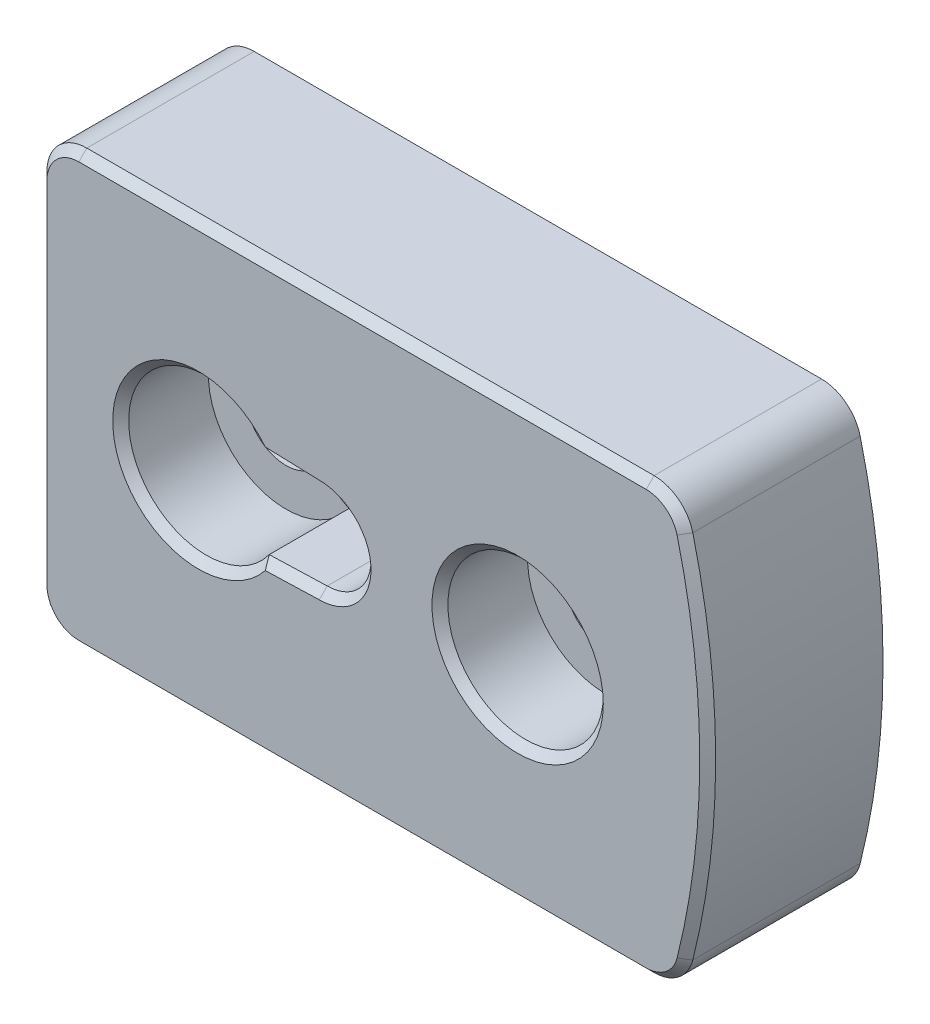
SolidWorks part; units mm, degrees
ref_plane "Front Plane" through (0, 0, 0) normal (0, 0, 1) x (1, 0, 0)
ref_plane "Top Plane" through (0, 0, 0) normal (0, 1, 0) x (1, 0, 0)
ref_plane "Right Plane" through (0, 0, 0) normal (1, 0, 0) x (0, 0, -1)
sketch "Sketch1" plane through (0, 0, 0) normal (0, 0, 1) x (1, 0, 0)
  line L0 (-10, 13.5) -> (-10, -13.5) construction
  line L1 (-20, -13.5) -> (20, -13.5)
  line L2 (-20, -13.5) -> (-20, 13.5)
  line L3 (-20, 13.5) -> (20, 13.5)
  line L5 (-20, -13.5) -> (20, 13.5) construction
  line L6 (-20, 13.5) -> (20, -13.5) construction
  line L7 (10.0266, 13.5) -> (10.0266, -13.5) construction
  line L8 (-8.92, 0) -> (-8.92, -38.6748) construction
  line L13 (-8.92, -38.6748) -> (-10.28, -38.6748) construction
  line L14 (-10.28, -38.6748) -> (-10.28, 0) construction
  line L15 (-2.42, 6.5) -> (43.4398, 6.5) construction
  line L16 (43.4398, 6.5) -> (43.4398, 7.86) construction
  line L17 (43.4398, 7.86) -> (-2.42, 7.86) construction
  line L18 (20, -13.5) -> (19.9199, -28.5934)
  circle A0 centre (-2.42, 0) radius 6.5
  arc A1 (-10.28, 0) -> (-2.42, 7.86) centre (-2.42, 0) cw construction
  arc A2 (20, 13.5) -> (20, -13.5) centre (-25.7558, 0) cw
  point P0 (-2.4466, -2.4466)
  point P7 (21.95, 0)
  dimension "D3" = 13
  dimension "D6" = 1.36
  dimension "D8" = 17.58
  dimension "D9" = 1.95
  dimension "D1" = 5.64
  dimension "D2" = 40
  dimension "D4" = 10
  dimension "D5" = 27
  dimension "D7" = 1.36
extrude "Boss-Extrude1" add sketch "Sketch1" along normal blind 11 contours L1 L3 L2 A0 | A0 region at (-19.5011, 0, 0) region at (-2.42, 0, 0)
sketch "Sketch2" plane through (0, 0, 11) normal (0, 0, 1) x (1, 0, 0)
  line L0 (-10, 13.5) -> (-10, -13.5) construction
  line L1 (10.0266, 13.5) -> (10.0266, -13.5) construction
  circle A0 centre (-10, 0) radius 2.5
  circle A1 centre (10.0266, 0) radius 2.5
  dimension "D1" = 5
extrude "Cut-Extrude1" cut sketch "Sketch2" against normal through all
sketch "Sketch3" plane through (0, 0, 11) normal (0, 0, 1) x (1, 0, 0)
  line L0 (-10, 13.5) -> (-10, -13.5) construction
  line L1 (10.0266, 13.5) -> (10.0266, -13.5) construction
  circle A0 centre (-10, 0) radius 4.875
  circle A1 centre (10.0266, 0) radius 4.875
  dimension "D1" = 9.75
extrude "Cut-Extrude2" cut sketch "Sketch3" against normal offset from surface (5.5 mm away) 5.5 up to face at (-7.5, 0, 0)
sketch "Sketch4" plane through (0, 0, 11) normal (0, 0, 1) x (1, 0, 0)
  circle A0 centre (-2.42, 0) radius 2.75
  dimension "D1" = 5.5
extrude "Cut-Extrude3" cut sketch "Sketch4" against normal through all
sketch "Sketch5" plane through (0, 0, 0) normal (0, 0, -1) x (-1, 0, 0)
  line L1 (6.72, -2.4826) -> (6.72, 2.4826)
  line L2 (6.72, 2.4826) -> (2.42, 4.9652)
  line L3 (2.42, 4.9652) -> (-1.88, 2.4826)
  line L4 (-1.88, 2.4826) -> (-1.88, -2.4826)
  line L5 (-1.88, -2.4826) -> (2.42, -4.9652)
  line L6 (2.42, -4.9652) -> (6.72, -2.4826)
  line L7 (20, -13.5) -> (20, 13.5) construction
  circle A0 centre (2.42, 0) radius 4.3 construction
  dimension "D1" = 8.6
extrude "Cut-Extrude4" cut sketch "Sketch5" against normal up to surface (5.5 mm away) up to face at (-10.0225, 0, 5.5)
fillet "Fillet1" radius 2.5 4 edges at (-20, -13.5, 5.5) (-20, 13.5, 5.5) (20, -13.5, 5.5) (20, 13.5, 5.5)
chamfer "Chamfer1" distance 0.5 angle 45 8 edges at (0.2956, -13.5, 11) (-19.2678, -12.7678, 11) (-20, 0, 11) (-19.2678, 12.7678, 11) (0.2956, 13.5, 11) (19.629, -12.9711, 11) (21.95, 0, 11) (19.629, 12.9711, 11)
sketch "Sketch6" plane through (0, 0, 11) normal (0, 0, 1) x (1, 0, 0)
  line L5 (-6.0563, 2.8658) -> (-2.42, 2.75)
  line L6 (-6.0563, -2.8658) -> (-2.42, -2.75)
  line L7 (-6.0563, 2.8658) -> (-2.42, 4.9652) construction
  line L9 (-6.0563, -2.8658) -> (-6.72, -2.4826)
  line L12 (-6.72, 2.4826) -> (-2.42, 4.9652) construction
  line L13 (-6.72, -2.4826) -> (-6.72, 2.4826)
  line L19 (-6.72, 2.4826) -> (-6.0563, 2.8658)
  arc A0 (-5.1412, -0.397) -> (-5.1412, 0.397) centre (-2.42, 0) ccw construction
  arc A1 (-6.0563, 2.8658) -> (-6.0563, -2.8658) centre (-10, 0) ccw construction
  arc A2 (-2.42, -2.75) -> (-2.42, 2.75) centre (-2.42, 0) ccw
  arc A4 (-5.1412, 0.397) -> (-5.1412, -0.397) centre (-10, 0) ccw construction
extrude "Cut-Extrude5" cut sketch "Sketch6" against normal through all and the other way through all
fillet "Fillet2" [suppressed] radius 3
chamfer "Chamfer3" distance 0.5 angle 45 5 edges at (14.9016, 0, 11) (-4.2381, -2.8079, 11) (0.33, 0, 11) (-4.2381, 2.8079, 11) (-14.875, 0, 11)
